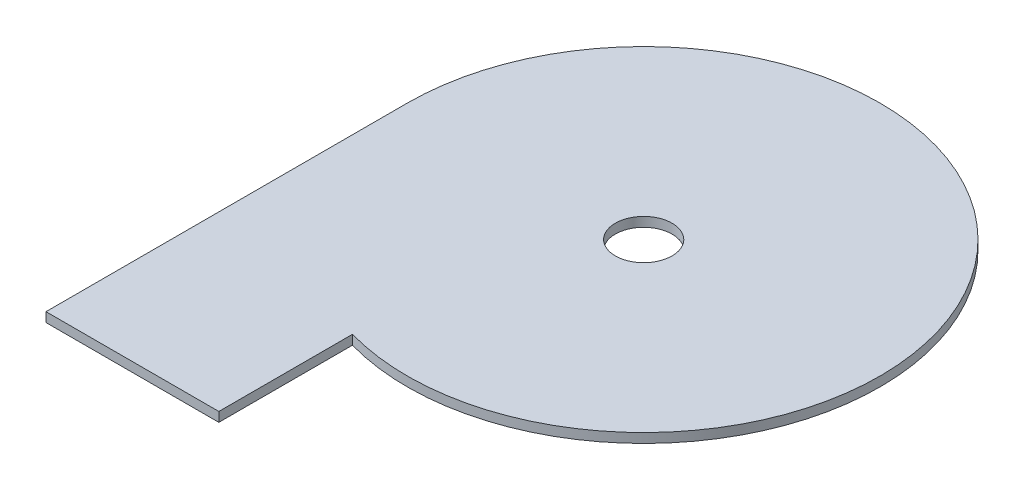
SolidWorks part; units mm, degrees
ref_plane "Front Plane" through (0, 0, 0) normal (0, 0, 1) x (1, 0, 0)
ref_plane "Top Plane" through (0, 0, 0) normal (0, 1, 0) x (1, 0, 0)
ref_plane "Right Plane" through (0, 0, 0) normal (1, 0, 0) x (0, 0, -1)
sketch "Sketch1" plane through (0, 0, 0) normal (0, 1, 0) x (1, 0, 0)
  circle A0 centre (0, 0) radius 50
extrude "Boss-Extrude1" add sketch "Sketch1" along normal blind 2
sketch "Sketch2" plane through (0, 2, 0) normal (0, 1, 0) x (1, 0, 0)
  circle A0 centre (0, 0) radius 6
extrude "Cut-Extrude1" cut sketch "Sketch2" against normal blind 2
sketch "Sketch3" plane through (0, 0, 0) normal (0, -1, 0) x (1, 0, 0)
  line L1 (-50, 0) -> (-13.4445, 0)
  line L2 (-50, 0) -> (-50, 76.4199)
  line L3 (-50, 76.4199) -> (-13.4445, 76.4199)
  line L4 (-13.4445, 0) -> (-13.4445, 76.4199)
  circle A0 centre (0, 0) radius 50 construction
  point P6 (-13.4445, 0)
extrude "Boss-Extrude2" add sketch "Sketch3" against normal through all
sketch "Sketch4" plane through (0, 2, 0) normal (0, 1, 0) x (1, 0, 0)
  line L4 (-26, -48.23) -> (-26, -61.13)
  line L5 (-20.1, -48.23) -> (-26, -48.23)
  line L6 (-20.1, -61.13) -> (-20.1, -48.23)
  line L7 (-26, -61.13) -> (-20.1, -61.13)
  line L8 (-26, -48.23) -> (-26, -61.13)
  line L9 (-20.1, -48.23) -> (-26, -48.23)
  line L10 (-20.1, -61.13) -> (-20.1, -48.23)
  line L11 (-26, -61.13) -> (-20.1, -61.13)
  dimension "D1" = 0
